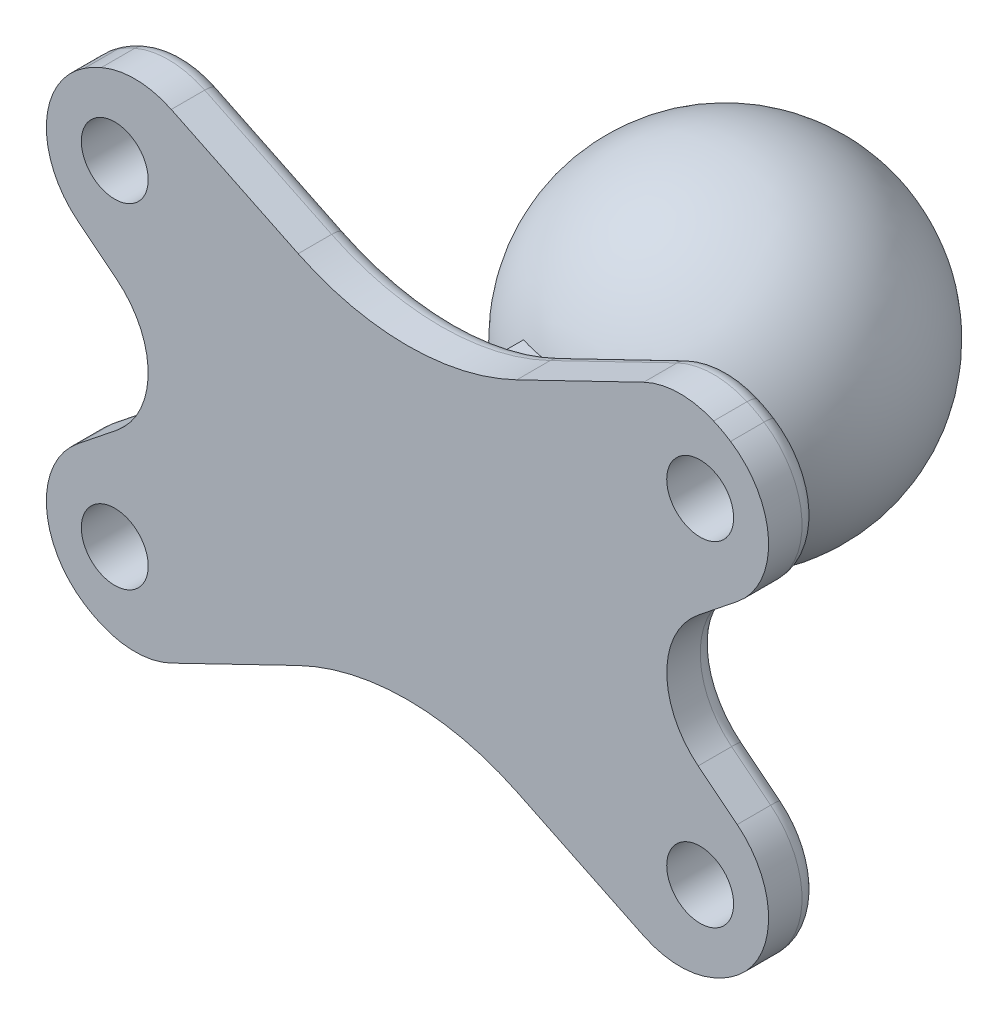
SolidWorks part; units mm, degrees
ref_plane "Front Plane" through (0, 0, 0) normal (0, 0, 1) x (1, 0, 0)
ref_plane "Top Plane" through (0, 0, 0) normal (0, 1, 0) x (1, 0, 0)
ref_plane "Right Plane" through (0, 0, 0) normal (1, 0, 0) x (0, 0, -1)
sketch "Sketch1" plane through (0, 0, -3) normal (0, 0, -1) x (-1, 0, 0)
  line L0 (-22.0785, 93.9573) -> (-14.4892, 97.6296)
  line L1 (-23.4558, 123.2909) -> (7.5442, 123.2909) construction
  line L2 (-30.4558, 116.2909) -> (-30.4558, 100.2909) construction
  line L3 (-23.4558, 93.2909) -> (7.5442, 93.2909) construction
  line L4 (14.5442, 116.2909) -> (14.5442, 100.2909) construction
  line L5 (-1.4224, 97.6296) -> (6.167, 93.9573)
  line L6 (11.7589, 114.0626) -> (9.4247, 112.1952)
  line L7 (9.4247, 104.3865) -> (11.7589, 102.5191)
  line L8 (6.167, 122.6245) -> (-1.4224, 118.9522)
  line L9 (-14.4892, 118.9522) -> (-22.0785, 122.6245)
  line L10 (-27.6705, 114.0626) -> (-25.3362, 112.1952)
  line L11 (-25.3362, 104.3865) -> (-27.6705, 102.5191)
  line L12 (-7.9558, 115.7909) -> (-7.9558, 100.7909) construction
  line L13 (-20.4558, 108.2909) -> (4.5442, 108.2909) construction
  circle A0 centre (-25.4558, 118.2909) radius 2
  circle A1 centre (9.5442, 118.2909) radius 2
  circle A2 centre (-25.4558, 98.2909) radius 2
  circle A3 centre (9.5442, 98.2909) radius 2
  arc A4 (-27.275, 122.1572) -> (-26.2577, 122.7057) centre (-23.4558, 116.2909) cw
  arc A5 (-26.2577, 93.8761) -> (-27.275, 94.4246) centre (-23.4558, 100.2909) cw
  arc A6 (11.3634, 94.4246) -> (10.3461, 93.8761) centre (7.5442, 100.2909) cw
  arc A7 (11.3634, 122.1572) -> (10.3461, 122.7057) centre (7.5442, 116.2909) ccw
  arc A8 (-25.3362, 104.3865) -> (-25.3362, 112.1952) centre (-28.4597, 108.2909) ccw
  arc A9 (9.4247, 104.3865) -> (9.4247, 112.1952) centre (12.5481, 108.2909) cw
  arc A10 (-1.4224, 118.9522) -> (-14.4892, 118.9522) centre (-7.9558, 132.4546) cw
  arc A11 (-1.4224, 97.6296) -> (-14.4892, 97.6296) centre (-7.9558, 84.1272) ccw
  arc A12 (-27.6705, 114.0626) -> (-27.275, 122.1572) centre (-24.547, 117.967) cw
  arc A13 (-22.0785, 122.6245) -> (-26.2577, 122.7057) centre (-24.2563, 118.1237) ccw
  arc A14 (11.7589, 114.0626) -> (11.3634, 122.1572) centre (8.6354, 117.967) ccw
  arc A15 (6.167, 122.6245) -> (10.3461, 122.7057) centre (8.3448, 118.1237) cw
  arc A16 (11.3634, 94.4246) -> (11.7589, 102.5191) centre (8.6354, 98.6148) ccw
  arc A17 (6.167, 93.9573) -> (10.3461, 93.8761) centre (8.3448, 98.4581) ccw
  arc A18 (-27.275, 94.4246) -> (-27.6705, 102.5191) centre (-24.547, 98.6148) cw
  arc A19 (-22.0785, 93.9573) -> (-26.2577, 93.8761) centre (-24.2563, 98.4581) cw
  point P28 (-7.9558, 108.2909)
  point P29 (14.5442, 108.2909)
  point P30 (-7.9558, 108.2909)
  point P31 (-7.9558, 123.2909)
  dimension "D5" = 7
  dimension "D6" = 7
  dimension "D7" = 7
  dimension "D8" = 7
  dimension "D11" = 5
  dimension "D12" = 5
  dimension "D13" = 15
  dimension "D14" = 15
  dimension "D15" = 5
  dimension "D16" = 5
  dimension "D17" = 5
  dimension "D18" = 5
  dimension "D19" = 5
  dimension "D20" = 5
  dimension "D21" = 5
  dimension "D22" = 5
  dimension "D1" = 5
  dimension "D2" = 5
  dimension "D3" = 5
  dimension "D4" = 5
  dimension "D9" = 15
  dimension "D10" = 25
extrude "Boss-Extrude1" add sketch "Sketch1" along normal blind 3
fillet "Fillet1" radius 1 2 edges at (18.2839, 95.7934, -6) (7.9558, 99.1272, -6) type face fillet first side face at (23.4558, 98.2909, -6) second side face at (7.9558, 98.3784, -4.5) second side face at (18.2839, 95.7934, -4.5)
sketch "Sketch2" plane through (0, 0, -6) normal (0, 0, -1) x (-1, 0, 0)
  line L0 (-22.4597, 108.2909) -> (6.5481, 108.2909) construction
  line L1 (-10.9558, 111.2909) -> (-4.9558, 111.2909)
  line L2 (-10.9558, 111.2909) -> (-10.9558, 105.2909)
  line L3 (-10.9558, 105.2909) -> (-4.9558, 105.2909)
  line L4 (-4.9558, 111.2909) -> (-4.9558, 105.2909)
  line L5 (-7.9558, 100.1272) -> (-7.9558, 116.4546) construction
  arc A0 (-24.7115, 103.6057) -> (-24.7115, 112.9761) centre (-28.4597, 108.2909) ccw construction
  arc A1 (8.8, 112.9761) -> (8.8, 103.6057) centre (12.5481, 108.2909) ccw construction
  arc A2 (-14.9248, 118.0521) -> (-0.9868, 118.0521) centre (-7.9558, 132.4546) ccw construction
  arc A3 (-0.9868, 98.5297) -> (-14.9248, 98.5297) centre (-7.9558, 84.1272) ccw construction
  dimension "D1" = 3
  dimension "D2" = 6
  dimension "D3" = 3
  dimension "D4" = 6
extrude "Boss-Extrude2" add sketch "Sketch2" along normal blind 13
fillet "Fillet4" radius 1 4 edges at (7.9558, 105.2909, -6) (10.9558, 108.2909, -6) (7.9558, 111.2909, -6) (4.9558, 108.2909, -6) type face fillet first side face at (7.9558, 108.2909, -6) second side face at (4.9558, 108.2909, -12.5) second side face at (7.9558, 111.2909, -12.5) second side face at (10.9558, 108.2909, -12.5) second side face at (7.9558, 105.2909, -12.5)
ref_point "Point1"
ref_axis "Axis1" through (7.9558, 108.2909, -19) along (0, 0, -1)
ref_plane "Plane1" through (0, 108.2909, 0) normal (0, 1, 0) x (0, 0, -1)
sketch "Sketch3" plane through (0, 108.2909, 0) normal (0, 1, 0) x (0, 0, -1)
  line L1 (19, -4.9558) -> (19, -10.9558) construction
  circle A0 centre (23, -7.9558) radius 10
  dimension "D1" = 20
  dimension "D2" = 4
sketch "Sketch4" plane through (0, 108.2909, 0) normal (0, 1, 0) x (0, 0, -1)
  line L1 (19, -4.9558) -> (19, -10.9558) construction
  line L2 (12, -7.9558) -> (32, -7.9558)
  arc A0 (12, -7.9558) -> (32, -7.9558) centre (22, -7.9558) ccw
  dimension "D2" = 20
  dimension "D1" = 3
revolve "Revolve2" add sketch "Sketch4" angle 360 about L2
